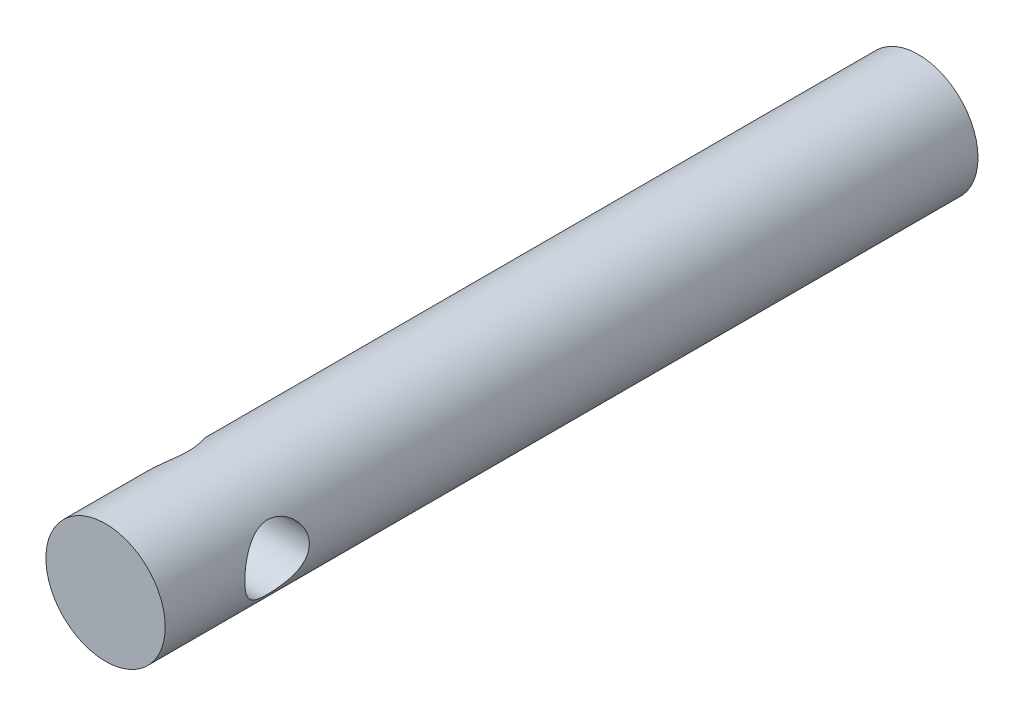
SolidWorks part; units mm, degrees
ref_plane "Front Plane" through (0, 0, 0) normal (0, 0, 1) x (1, 0, 0)
ref_plane "Top Plane" through (0, 0, 0) normal (0, 1, 0) x (1, 0, 0)
ref_plane "Right Plane" through (0, 0, 0) normal (1, 0, 0) x (0, 0, -1)
sketch "Sketch1" plane through (0, 0, 0) normal (0, 0, 1) x (1, 0, 0)
  circle A0 centre (0, 0) radius 4
extrude "Boss-Extrude1" add sketch "Sketch1" along normal blind 54.5
sketch "Sketch2" plane through (0, 0, 0) normal (1, 0, 0) x (0, 0, -1)
  line L0 (-54.5, -4) -> (0, -4) construction
  line L1 (-54.5, 4) -> (-39.5, 4) construction
  line L2 (-54.5, 4) -> (-54.5, -4) construction
  line L3 (-54.5, -4) -> (-39.5, -4) construction
  line L4 (-39.5, 4) -> (-39.5, -4) construction
  line L5 (-54.5, 4) -> (-39.5, -4) construction
  line L6 (-39.5, 4) -> (-54.5, -4) construction
  circle A0 centre (-47, 0) radius 2.165
  dimension "D2" = 4.33
  dimension "D1" = 15
extrude "Cut-Extrude1" cut sketch "Sketch2" against normal mid plane 18
sketch "Sketch4" plane through (0, 0, 0) normal (1, 0, 0) x (0, 0, -1)
  circle A0 centre (-47, 0) radius 3.5
extrude "Cut-Extrude2" cut sketch "Sketch4" against normal through all
